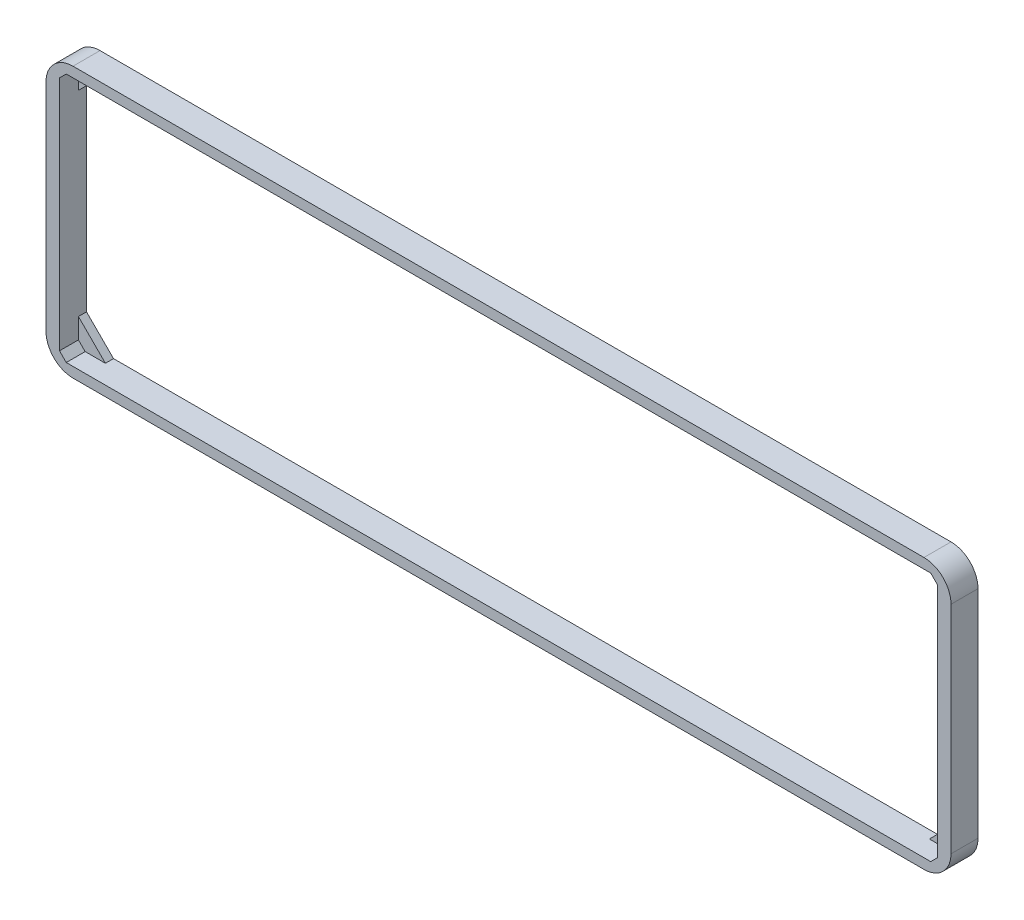
SolidWorks part; units mm, degrees
ref_plane "Front Plane" through (0, 0, 0) normal (0, 0, 1) x (1, 0, 0)
ref_plane "Top Plane" through (0, 0, 0) normal (0, 1, 0) x (1, 0, 0)
ref_plane "Right Plane" through (0, 0, 0) normal (1, 0, 0) x (0, 0, -1)
sketch "Sketch1" plane through (0, 0, 0) normal (0, 0, 1) x (1, 0, 0)
  line L1 (-167.5, -50) -> (167.5, -50)
  line L2 (-167.5, -50) -> (-167.5, 50)
  line L3 (-167.5, 50) -> (167.5, 50)
  line L4 (167.5, -50) -> (167.5, 50)
  line L5 (-167.5, -50) -> (167.5, 50) construction
  line L6 (-167.5, 50) -> (167.5, -50) construction
  line L7 (-162.5, -46.25) -> (162.5, -46.25)
  line L8 (-162.5, -46.25) -> (-162.5, 46.25)
  line L9 (-162.5, 46.25) -> (162.5, 46.25)
  line L10 (162.5, -46.25) -> (162.5, 46.25)
  line L11 (-162.5, -46.25) -> (162.5, 46.25) construction
  line L12 (-162.5, 46.25) -> (162.5, -46.25) construction
  point P0 (0, 0)
  point P6 (0, 0)
  dimension "D1" = 335
  dimension "D2" = 100
  dimension "D3" = 325
  dimension "D4" = 92.5
extrude "Boss-Extrude1" add sketch "Sketch1" against normal blind 10
fillet "Fillet1" radius 10 4 edges at (-167.5, 50, -5) (-167.5, -50, -5) (167.5, -50, -5) (167.5, 50, -5)
sketch "Sketch2" plane through (0, 0, -10) normal (0, 0, -1) x (-1, 0, 0)
  line L0 (-162.5, -46.25) -> (-162.5, -36.25)
  line L1 (-162.5, -46.25) -> (-162.5, 46.25) construction
  line L2 (-162.5, -36.25) -> (-152.5, -46.25)
  line L3 (162.5, -46.25) -> (-162.5, -46.25) construction
  line L4 (-152.5, -46.25) -> (-162.5, -46.25)
  line L5 (-162.5, 46.25) -> (-152.5, 46.25)
  line L6 (-162.5, 46.25) -> (162.5, 46.25) construction
  line L7 (-152.5, 46.25) -> (-162.5, 36.25)
  line L8 (-162.5, 36.25) -> (-162.5, 46.25)
  line L9 (162.5, 46.25) -> (152.5, 46.25)
  line L10 (152.5, 46.25) -> (162.5, 36.25)
  line L11 (162.5, 46.25) -> (162.5, -46.25) construction
  line L12 (162.5, 36.25) -> (162.5, 46.25)
  line L13 (162.5, -46.25) -> (162.5, -36.25)
  line L14 (162.5, -36.25) -> (152.5, -46.25)
  line L15 (152.5, -46.25) -> (162.5, -46.25)
  dimension "D1" = 10
  dimension "D2" = 10
  dimension "D3" = 10
  dimension "D4" = 10
  dimension "D5" = 10
  dimension "D6" = 10
  dimension "D7" = 10
  dimension "D8" = 10
extrude "Boss-Extrude2" add sketch "Sketch2" against normal blind 3
chamfer "Chamfer1" distance 2.5 angle 45 4 edges at (162.5, -46.25, -3.5) (162.5, 46.25, -3.5) (-162.5, -46.25, -3.5) (-162.5, 46.25, -3.5)
